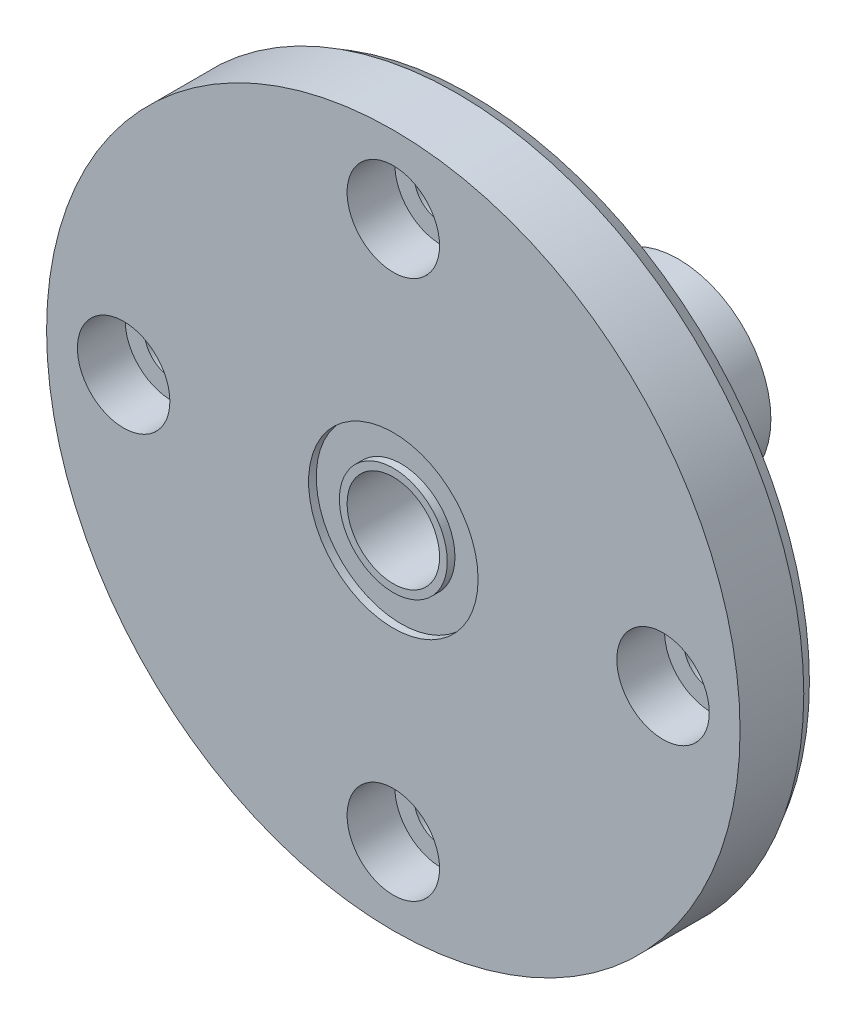
SolidWorks part; units mm, degrees
ref_plane "Front Plane" through (0, 0, 0) normal (0, 0, 1) x (1, 0, 0)
ref_plane "Top Plane" through (0, 0, 0) normal (0, 1, 0) x (1, 0, 0)
ref_plane "Right Plane" through (0, 0, 0) normal (1, 0, 0) x (0, 0, -1)
sketch "Sketch1" plane through (0, 0, 0) normal (0, 0, 1) x (1, 0, 0)
  circle A0 centre (0, 0) radius 22.5
  circle A1 centre (0, 0) radius 3
  dimension "D1" = 45
  dimension "D2" = 6
extrude "Boss-Extrude1" add sketch "Sketch1" along normal blind 5
sketch "Sketch2" plane through (0, 0, 0) normal (0, 0, -1) x (-1, 0, 0)
  circle A0 centre (0, 0) radius 3
  circle A1 centre (0, 0) radius 3 construction
  circle A2 centre (0, 0) radius 6
  dimension "D1" = 12
extrude "Boss-Extrude2" add sketch "Sketch2" along normal blind 14
sketch "Sketch3" plane through (0, 0, 5) normal (0, 0, 1) x (1, 0, 0)
  line L0 (0, 17.5) -> (0, -17.5) construction
  line L1 (-17.5, 0) -> (17.5, 0) construction
  circle A0 centre (0, 0) radius 17.5 construction
  circle A1 centre (-17.5, 0) radius 1.75
  circle A2 centre (0, -17.5) radius 1.75
  circle A3 centre (17.5, 0) radius 1.75
  circle A4 centre (0, 17.5) radius 1.75
  dimension "D1" = 35
  dimension "D2" = 3.5
extrude "Cut-Extrude1" cut sketch "Sketch3" against normal through all
sketch "Sketch4" plane through (0, 0, 5) normal (0, 0, 1) x (1, 0, 0)
  circle A0 centre (-17.5, 0) radius 3
  circle A1 centre (0, -17.5) radius 3
  circle A2 centre (0, -17.5) radius 1.75 construction
  circle A3 centre (17.5, 0) radius 3
  circle A4 centre (0, 17.5) radius 3
  circle A5 centre (0, 17.5) radius 1.75 construction
  dimension "D1" = 6
extrude "Cut-Extrude2" cut sketch "Sketch4" against normal blind 3.1
sketch "Sketch5" plane through (0, 0, 5) normal (0, 0, 1) x (1, 0, 0)
  circle A0 centre (0, 0) radius 5.5
  circle A1 centre (0, 0) radius 3 construction
  circle A2 centre (0, 0) radius 3.5
  dimension "D1" = 2.5
  dimension "D2" = 0.5
extrude "Cut-Extrude3" cut sketch "Sketch5" against normal blind 0.5
sketch "Sketch6" plane through (0, 0, -14) normal (0, 0, -1) x (-1, 0, 0)
  circle A0 centre (0, 0) radius 3.5
  circle A2 centre (0, 0) radius 3 construction
  circle A3 centre (0, 0) radius 5.5
  circle A4 centre (0, 0) radius 5.5 construction
  dimension "D1" = 0.5
extrude "Cut-Extrude4" cut sketch "Sketch6" against normal blind 0.5
chamfer "Chamfer1" distance 0.5 angle 60 6 edges at (1.75, -17.5, 0) (19.25, 0, 0) (-15.75, 0, 0) (1.75, 17.5, 0) (22.5, 0, 0) (-6, 0, -14) first distance on face at (1.75, -17.5, 0) first distance on face at (19.25, 0, 0) first distance on face at (-15.75, 0, 0) first distance on face at (1.75, 17.5, 0) first distance on face at (-6, 0, -14)
chamfer "Chamfer2" distance 0.2 angle 60 1 edges at (-3, 0, -14) first distance on face at (-3, 0, -14)
chamfer "Chamfer3" distance 0.1 angle 60 1 edges at (-3.5, 0, -14) first distance on face at (-3.5, 0, -13.5)
